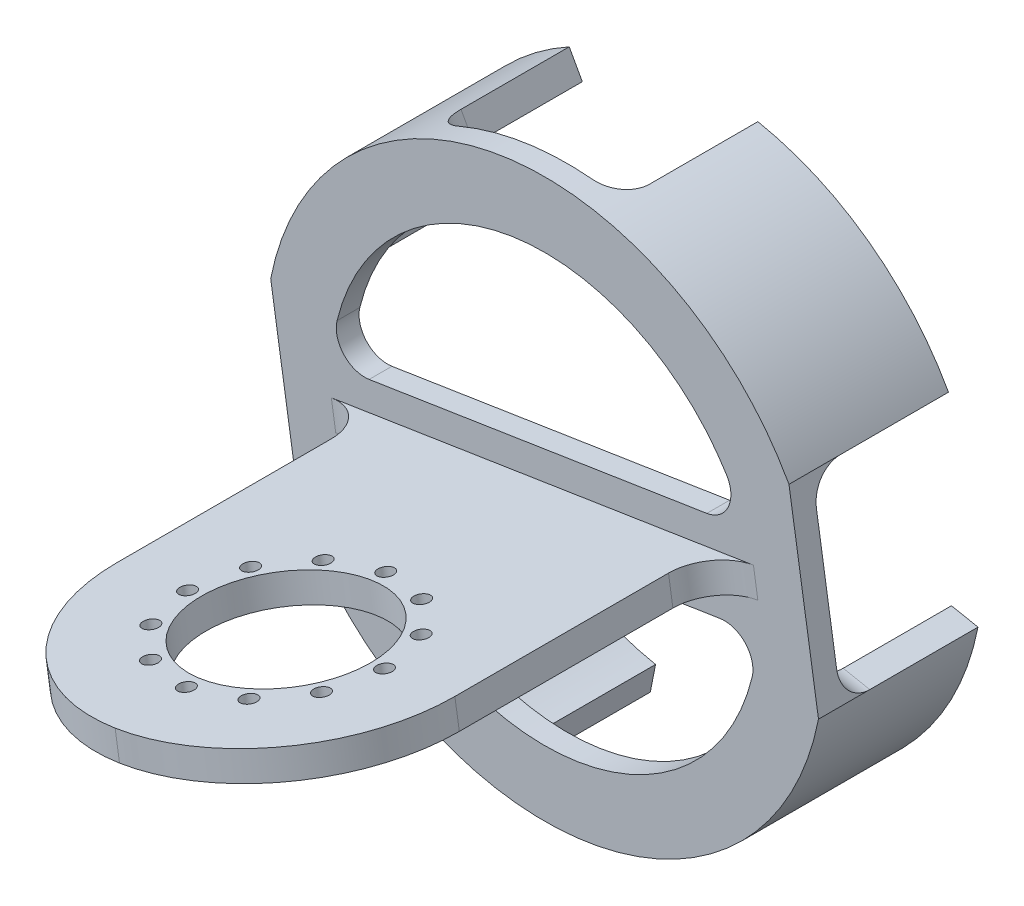
SolidWorks part; units mm, degrees
material "1.0035 (S185)"
ref_plane "前视基准面" through (0, 0, 0) normal (0, 0, 1) x (1, 0, 0)
ref_plane "上视基准面" through (0, 0, 0) normal (0, 1, 0) x (1, 0, 0)
ref_plane "右视基准面" through (0, 0, 0) normal (1, 0, 0) x (0, 0, -1)
sketch "草图1" plane through (0, 0, 0) normal (0, 0, 1) x (1, 0, 0)
  circle A0 centre (0, 0) radius 70
  circle A1 centre (0, 0) radius 88.5
  dimension "D1" = 140
  dimension "D2" = 177
extrude "凸台-拉伸1" add sketch "草图1" along normal blind 8
sketch "草图2" plane through (0, 0, 8) normal (0, 0, 1) x (1, 0, 0)
  circle A0 centre (0, 0) radius 81.25 construction
  circle A1 centre (15.5646, 79.7452) radius 2.75
  circle A2 centre (42.0516, 69.5214) radius 2.75
  circle A3 centre (53.352, 61.2791) radius 2.75
  circle A4 centre (71.1784, 39.1816) radius 2.75
  arc A5 (18.331, 80.1781) -> (12.7983, 79.3124) centre (15.5646, 79.7452) ccw construction
  dimension "D1" = 162.5
  dimension "D2" = 5.5
extrude "切除-拉伸1" cut sketch "草图2" against normal blind 10
pattern_circular "阵列(圆周)1" count 4 over 360 about axis through (0, 0, 8) along (0, 0, 1) of "切除-拉伸1"
sketch "草图3" plane through (0, 0, 8) normal (0, 0, 1) x (1, 0, 0)
  line L0 (0, 0) -> (-71.1784, -39.1816) construction
  line L1 (0, 0) -> (-89.3496, 25.8001) construction
  line L2 (0, 0) -> (-129.4054, -20.2497) construction
  line L3 (0, 0) -> (-19.2768, 123.1882) construction
  line L4 (0, 0) -> (-104.6553, 76.3337) construction
  line L5 (-42.7619, 77.4833) -> (-47.3522, 85.8008)
  line L6 (-86.8425, 17.0478) -> (-96.1646, 18.8778)
  arc A0 (-42.7619, 77.4833) -> (-86.8425, 17.0478) centre (0, 0) ccw
  arc A1 (-47.3522, 85.8008) -> (-96.1646, 18.8778) centre (0, 0) ccw
  circle A2 centre (0, 0) radius 93 construction
  circle A6 centre (0, 0) radius 88.5 construction
  point P8 (-75.137, 54.8036)
  point P12 (-51.8618, 77.1969)
  dimension "D4" = 98
  dimension "D5" = 186
  dimension "D1" = 45
  dimension "D2" = 25
  dimension "D3" = 25
  dimension "D7" = 20
extrude "凸台-拉伸2" add sketch "草图3" against normal blind 56
pattern_circular "阵列(圆周)2" count 4 over 360 about axis through (0, 0, 8) along (0, 0, 1) of "凸台-拉伸2"
sketch "草图5" plane through (0, 0, -48) normal (0, 0, -1) x (-1, 0, 0)
  point P0 (89.3496, 25.8001)
  point P1 (75.137, 54.8036)
  point P2 (51.8618, 77.1969)
sketch "草图7" plane through (0, 0, 8) normal (0, 0, 1) x (1, 0, 0)
  circle A0 centre (0, 0) radius 98
  arc A1 (-47.3522, 85.8008) -> (-96.1646, 18.8778) centre (0, 0) ccw construction
extrude "凸台-拉伸3" add sketch "草图7" against normal up to surface (8 mm away) up to face at (-76.9952, 15.5646, 0)
hole_wizard "M5 螺纹孔的螺纹孔钻头2" positions "3D草图2" profile "草图6" hole size "M5" standard "GB"
sketch3d "3D草图2"
  point P0 (-51.8618, 77.1969, -48)
  point P9 (-75.137, 54.8036, -48)
  point P12 (-89.3496, 25.8001, -48)
sketch "草图6" plane through (-51.8618, 77.1969, -48) normal (1, 0, 0) x (0, 1, 0)
  line L0 (0, 0) -> (0, 11.2618)
  line L1 (0, 11.2618) -> (2.1, 10)
  line L2 (2.1, 10) -> (2.1, 0)
  line L5 (2.1, 0) -> (0, 0)
  line L10 (0, 11.2618) -> (-2.1, 10) construction
  line L11 (0, -6.35) -> (0, 107.95) construction
  dimension "孔直径" = 4.2
  dimension "孔深度" = 10
  dimension "导头角度" = 118
pattern_circular "阵列(圆周)3" count 4 over 360 about axis through (0, 0, 0) along (0, 0, -1) of "M5 螺纹孔的螺纹孔钻头2"
sketch "草图8" plane through (0, 0, 8) normal (0, 0, 1) x (1, 0, 0)
  line L0 (0, 0) -> (166.56, 26.0637) construction
  line L1 (-60.0516, -4.3362) -> (58.5056, 14.216)
  line L2 (-60.0516, -4.3362) -> (-58.5056, -14.216)
  line L3 (58.5056, 14.216) -> (60.0516, 4.3362)
  line L4 (-58.5056, -14.216) -> (60.0516, 4.3362)
  line L5 (-60.0516, -4.3362) -> (60.0516, 4.3362) construction
  line L6 (58.5056, 14.216) -> (-58.5056, -14.216) construction
  point P3 (89.3496, -25.8001)
  point P4 (77.1969, 51.8618)
  dimension "D1" = 10
  dimension "D2" = 120
extrude "凸台-拉伸4" add sketch "草图8" along normal blind 150
sketch "草图9" plane through (0.773, -4.9399, 0) normal (0.1546, -0.988, 0) x (0.988, 0.1546, 0)
  line L0 (-60, 8) -> (60, 8) construction
  circle A0 centre (0, 98) radius 35 construction
  circle A1 centre (0, 133) radius 2.75
  circle A2 centre (17.5, 128.3109) radius 2.75
  circle A3 centre (30.3109, 115.5) radius 2.75
  circle A4 centre (35, 98) radius 2.75
  circle A5 centre (30.3109, 80.5) radius 2.75
  circle A6 centre (17.5, 67.6891) radius 2.75
  circle A7 centre (0, 63) radius 2.75
  circle A8 centre (-17.5, 67.6891) radius 2.75
  circle A9 centre (-30.3109, 80.5) radius 2.75
  circle A10 centre (-35, 98) radius 2.75
  circle A11 centre (-30.3109, 115.5) radius 2.75
  circle A12 centre (-17.5, 128.3109) radius 2.75
  circle A13 centre (0, 98) radius 30
  point P29 (0, 98)
  dimension "D1" = 70
  dimension "D2" = 5.5
  dimension "D4" = 60
  dimension "D5" = 90
  dimension "D3" = 12
extrude "切除-拉伸2" cut sketch "草图9" against normal blind 187
fillet "圆角1" radius 60 2 edges at (59.2786, 9.2761, 158) (-59.2786, -9.2761, 158)
sketch "草图10" plane through (0, 0, 8) normal (0, 0, 1) x (1, 0, 0)
  line L0 (-74.9202, 3.4588) -> (70.2822, 26.1805)
  line L2 (74.9202, -3.4588) -> (-70.2822, -26.1805)
  line L3 (58.5056, 14.216) -> (-0.773, 4.9399) construction
  arc A0 (70.2822, 26.1805) -> (-74.9202, 3.4588) centre (0, 0) ccw
  arc A1 (-70.2822, -26.1805) -> (74.9202, -3.4588) centre (0, 0) ccw
  dimension "D3" = 150
  dimension "D1" = 15
  dimension "D2" = 15
extrude "切除-拉伸3" cut sketch "草图10" against normal blind 10
fillet "圆角2" radius 10 4 edges at (70.2822, 26.1805, 4) (-74.9202, 3.4588, 4) (-70.2822, -26.1805, 4) (74.9202, -3.4588, 4)
sketch "草图11" plane through (0, 0, 8) normal (0, 0, 1) x (1, 0, 0)
  line L0 (-96.1646, 18.8778) -> (-85.8008, -47.3522)
  line L1 (-85.8008, -47.3522) -> (-121.4935, -47.3522)
  line L2 (-121.4935, -47.3522) -> (-96.1646, 18.8778)
  line L3 (85.8008, 47.3522) -> (96.1646, -18.8778)
  line L4 (96.1646, -18.8778) -> (116.1298, 14.2372)
  line L5 (116.1298, 14.2372) -> (85.8008, 47.3522)
extrude "切除-拉伸4" cut sketch "草图11" against normal blind 10
fillet "圆角3" radius 10 8 edges at (17.9628, 91.5036, 0) (-45.0571, 81.6421, 0) (-91.5036, 17.9628, 0) (-81.6421, -45.0571, 0) (-17.9628, -91.5036, 0) (45.0571, -81.6421, 0) (91.5036, -17.9628, 0) (81.6421, 45.0571, 0)
fillet "圆角4" radius 15 2 edges at (59.2786, 9.2761, 8) (-59.2786, -9.2761, 8)
